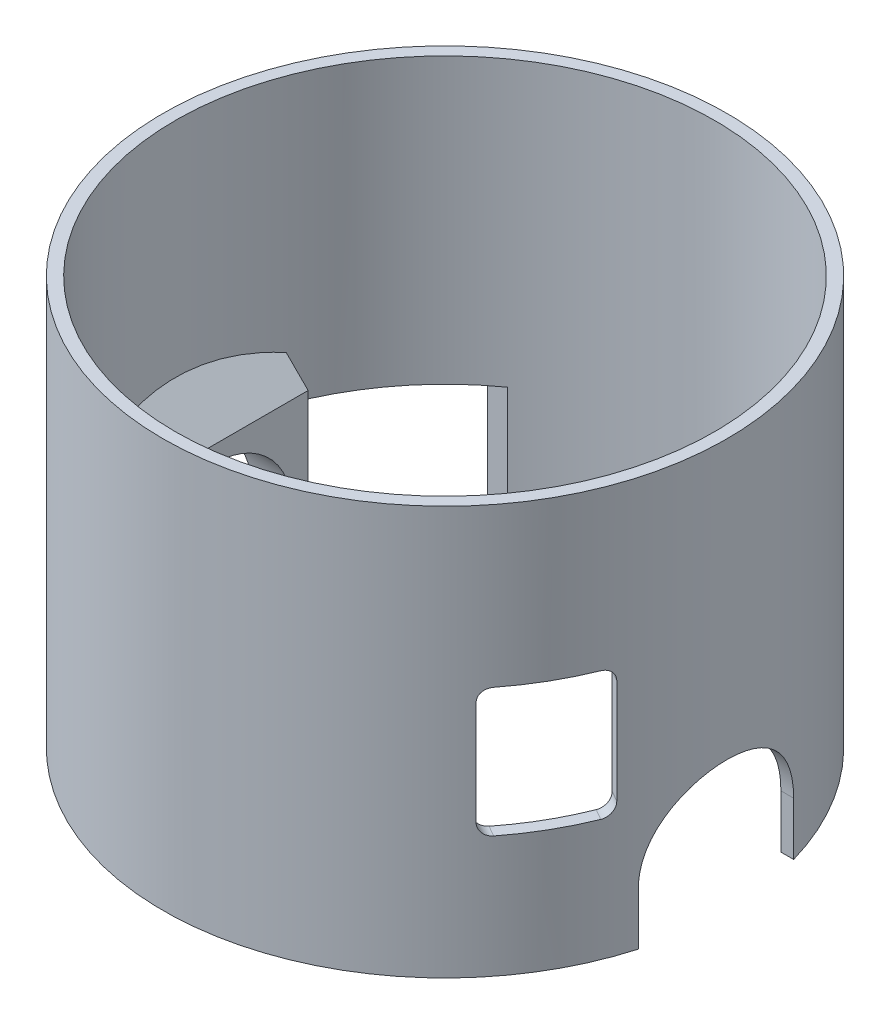
SolidWorks part; units mm, degrees
ref_plane "Front Plane" through (0, 0, 0) normal (0, 0, 1) x (1, 0, 0)
ref_plane "Top Plane" through (0, 0, 0) normal (0, 1, 0) x (1, 0, 0)
ref_plane "Right Plane" through (0, 0, 0) normal (1, 0, 0) x (0, 0, -1)
sketch "Sketch1" plane through (0, 0, 0) normal (0, 1, 0) x (1, 0, 0)
  circle A0 centre (0, 0) radius 69
  circle A1 centre (0, 0) radius 66
  dimension "D1" = 138
  dimension "D2" = 3
extrude "Boss-Extrude1" add sketch "Sketch1" along normal blind 100
sketch "Sketch2" plane through (0, 0, 0) normal (0, 1, 0) x (1, 0, 0)
  line L0 (0, 0) -> (-101.9987, 0) construction
  line L1 (0, 0) -> (-90.6575, -52.3411) construction
  line L2 (-64.9519, -37.5) -> (-82.6631, -6.8233) construction
  line L3 (0.25, -0.25) -> (126.3516, -0.25) construction
  line L4 (0.25, -0.25) -> (106.5028, -61.5951) construction
  line L5 (64.9062, -37.5792) -> (82.115, -7.7727) construction
  dimension "D1" = 30
  dimension "D2" = 75
  dimension "D3" = 30
  dimension "D4" = 75
ref_plane "Plane1" through (-64.9519, 0, 37.5) normal (0.866, 0, -0.5) x (-0.5, 0, -0.866)
sketch "Sketch3" plane through (-64.9519, 0, 37.5) normal (0.866, 0, -0.5) x (-0.5, 0, -0.866)
  line L0 (10, 31.5) -> (10, 59.5)
  line L1 (10, 59.5) -> (-10, 59.5)
  line L2 (-10, 59.5) -> (-10, 31.5)
  line L3 (-10, 31.5) -> (10, 31.5)
  point P2 (0, 31.5)
  dimension "D1" = 20
  dimension "D2" = 31.5
  dimension "D3" = 28
  dimension "D4" = 0
extrude "Cut-Extrude1" cut sketch "Sketch3" along normal up to next
fillet "Fillet1" radius 3 4 edges at (-52.8113, 31.5, 42.0376) (-62.8113, 31.5, 24.7171) (-52.8113, 59.5, 42.0376) (-62.8113, 59.5, 24.7171)
sketch "Sketch4" plane through (0, 0, 0) normal (1, 0, 0) x (0, 0, -1)
  line L1 (23.3, 0) -> (53.7, 0)
  line L2 (23.3, 0) -> (23.3, 30.4)
  line L3 (23.3, 30.4) -> (53.7, 30.4)
  line L4 (53.7, 0) -> (53.7, 30.4)
  dimension "D1" = 30.4
  dimension "D2" = 30.4
  dimension "D3" = 0
  dimension "D4" = 23.3
extrude "Cut-Extrude2" cut sketch "Sketch4" against normal through all
sketch "Sketch5" plane through (0, 0, 0) normal (1, 0, 0) x (0, 0, -1)
  line L8 (19, 13) -> (19, -6)
  line L9 (19, -6) -> (-19, -6)
  line L10 (-19, -6) -> (-19, 13)
  arc A1 (19, 13) -> (-19, 13) centre (0, 13) ccw
  dimension "D1" = 19
extrude "Cut-Extrude6" cut sketch "Sketch5" along normal through all both and the other way through all
sketch "Sketch6" plane through (0, 0, 0) normal (1, 0, 0) x (0, 0, -1)
  line L0 (19, 13) -> (19, 0)
  line L2 (-19, 0) -> (-19, 13)
  line L3 (23, 13) -> (23, 0)
  line L4 (-23, 0) -> (-23, 13)
  line L5 (23, 0) -> (19, 0)
  line L6 (-19, 0) -> (-23, 0)
  arc A0 (19, 13) -> (-19, 13) centre (0, 13) ccw
  arc A1 (23, 13) -> (-23, 13) centre (0, 13) ccw
  dimension "D1" = 19
  dimension "D3" = 0
  dimension "D2" = 4
extrude "Boss-Extrude2" add sketch "Sketch6" against normal up to next from offset 56.5 offset against normal yes
sketch "Sketch7" plane through (-56.5, 0, 0) normal (1, 0, 0) x (0, 0, -1)
  line L0 (0, 36) -> (15, 36) construction
  arc A0 (23, 13) -> (-23, 13) centre (0, 13) ccw construction
  dimension "D1" = 15
ref_plane "Plane2" through (-10.25, -10.25, 0) normal (-0.7071, -0.7071, 0) x (0, 0, -1)
sketch "Sketch8" plane through (-10.25, -10.25, 0) normal (-0.7071, -0.7071, 0) x (0, 0, -1)
  line L0 (23, -39.9515) -> (23, -49.1439) construction
  line L1 (-23, -82.9515) -> (23, -82.9515)
  line L2 (-23, -82.9515) -> (-23, -47.9515)
  line L3 (-23, -47.9515) -> (23, -47.9515)
  line L4 (23, -82.9515) -> (23, -47.9515)
  line L5 (-23, -49.1439) -> (-23, -39.9515) construction
  line L6 (19, -39.9515) -> (23, -39.9515) construction
  dimension "D1" = 0
  dimension "D2" = 0
  dimension "D3" = 8
  dimension "D4" = 35
extrude "Boss-Extrude4" add sketch "Sketch8" along normal blind 30 contours L2 L1 L4 L3
sketch "Sketch9" plane through (0, 0, 0) normal (0, -1, 0) x (1, 0, 0)
  line L12 (63.206, 19) -> (66.3325, 19)
  line L13 (-66.3325, 19) -> (-56.5, 19)
  line L14 (-56.5, 19) -> (-56.5, 23)
  line L15 (-56.5, 23) -> (-61.8628, 23)
  line L18 (-56.5, 19) -> (-56.5, 23)
  line L19 (-56.5, 23) -> (-61.8628, 23)
  line L20 (-56.5, 19) -> (-56.5, -19)
  line L24 (-56.5, -19) -> (-66.3325, -19)
  line L25 (-64.947, -23.3) -> (-61.7504, -23.3)
  line L26 (-61.8628, -23) -> (-56.5, -23)
  line L27 (-56.5, -23) -> (-56.5, -19)
  line L30 (-61.8628, -23) -> (-56.5, -23)
  line L31 (-56.5, -23) -> (-56.5, -19)
  arc A6 (66.3325, 19) -> (-66.3325, 19) centre (0, 0) ccw
  arc A7 (63.206, 19) -> (-61.8628, 23) centre (0, 0) ccw
  arc A8 (66.3325, 19) -> (-66.3325, 19) centre (0, 0) ccw
  arc A9 (63.206, 19) -> (-61.8628, 23) centre (0, 0) ccw
  arc A10 (-66.3325, -19) -> (-66.3325, 19) centre (0, 0) ccw
  arc A11 (-61.8628, -23) -> (-61.8628, 23) centre (0, 0) ccw
  arc A12 (-66.3325, -19) -> (-64.947, -23.3) centre (0, 0) ccw
  arc A13 (-61.8628, -23) -> (-61.7504, -23.3) centre (0, 0) ccw
  arc A14 (-66.3325, -19) -> (-64.947, -23.3) centre (0, 0) ccw
  arc A15 (-61.8628, -23) -> (-61.7504, -23.3) centre (0, 0) ccw
  circle A16 centre (0, 0) radius 69
  arc A18 (-61.8628, -23) -> (-61.8628, 23) centre (0, 0) ccw
  line M15 (-66.3325, 19) -> (-56.5, 19)
  line M16 (-56.5, 19) -> (-56.5, 23)
  line M17 (-56.5, 23) -> (-61.8628, 23)
  arc M18 (-61.8628, 23) -> (63.206, 19) centre (0, 0) cw
  dimension "D1" = 0
  dimension "D2" = 0
extrude "Cut-Extrude7" cut sketch "Sketch9" against normal through all flip side to cut contours A16
extrude "Cut-Extrude8" cut sketch "Sketch9<3>" against normal through all contours L31 L30 A11 M15 M18 M17 M16 region at (1.7062, 0, 0)
sketch "Sketch9<3>" plane through (0, 0, 0) normal (0, -1, 0) x (1, 0, 0) same geometry as "Sketch9"
extrude "Cut-Extrude9" cut sketch "Sketch5<2>" against normal through all
sketch "Sketch5<2>" plane through (0, 0, 0) normal (1, 0, 0) x (0, 0, -1) same geometry as "Sketch5"
ref_plane "Plane3" through (64.9519, 0, 37.5) normal (0.866, 0, 0.5) x (0.5, 0, -0.866)
sketch "Sketch10" plane through (64.9519, 0, 37.5) normal (0.866, 0, 0.5) x (0.5, 0, -0.866)
  line L0 (-11.6, 61.25) -> (11.6, 61.25) construction
  line L1 (-12.6, 61.25) -> (12.6, 61.25)
  line L2 (-12.6, 61.25) -> (-12.6, 29.75)
  line L3 (-12.6, 29.75) -> (12.6, 29.75)
  line L4 (12.6, 61.25) -> (12.6, 29.75)
  line L5 (12.6, 60.25) -> (12.6, 30.75) construction
  line L6 (11.6, 29.75) -> (-11.6, 29.75) construction
  line L7 (-12.6, 30.75) -> (-12.6, 60.25) construction
  dimension "D1" = 0
  dimension "D2" = 0
  dimension "D3" = 0
  dimension "D4" = 0
extrude "Cut-Extrude10" cut sketch "Sketch10" against normal up to next contours L2 L3 L4 L1
fillet "Fillet2" radius 3 4 edges at (51.1287, 29.75, 44.0684) (51.1287, 61.25, 44.0684) (63.7287, 61.25, 22.2446) (63.7287, 29.75, 22.2446)
